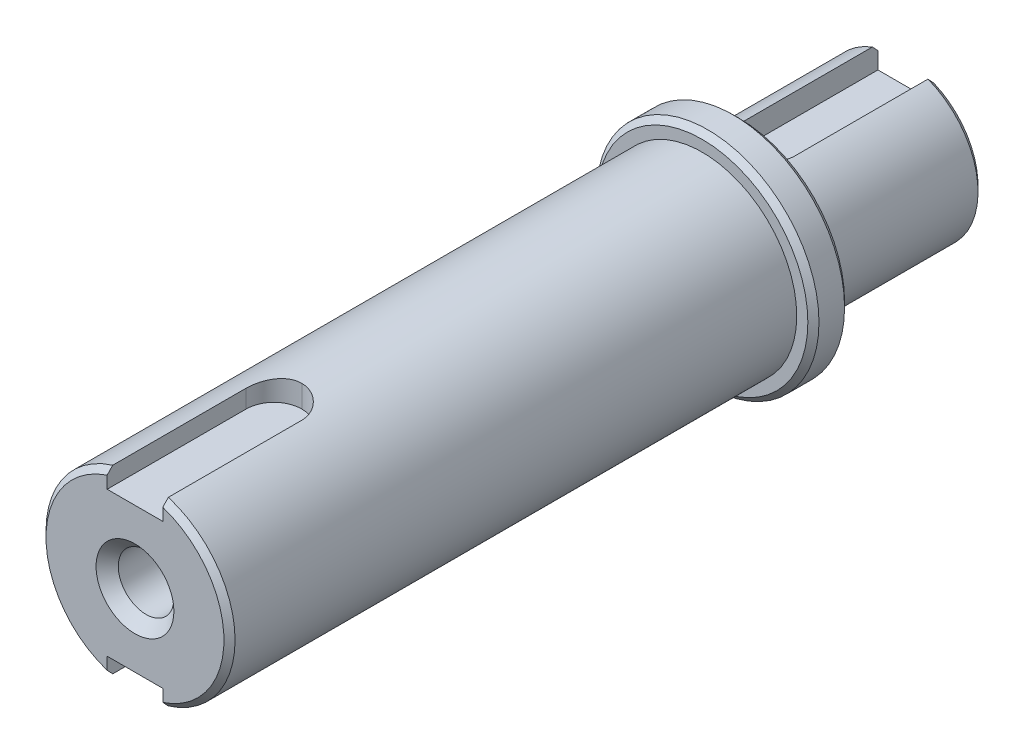
SolidWorks part; units mm, degrees
ref_plane "前视基准面" through (0, 0, 0) normal (0, 0, 1) x (1, 0, 0)
ref_plane "上视基准面" through (0, 0, 0) normal (0, 1, 0) x (1, 0, 0)
ref_plane "右视基准面" through (0, 0, 0) normal (1, 0, 0) x (0, 0, -1)
sketch "草图1" plane through (0, 0, 0) normal (0, 0, 1) x (1, 0, 0)
  circle A0 centre (0, 0) radius 7
  dimension "D1" = 14
extrude "拉伸1" add sketch "草图1" along normal blind 15
sketch "草图3" plane through (0, 0, 15) normal (0, 0, 1) x (1, 0, 0)
  circle A0 centre (0, 0) radius 10
extrude "拉伸2" add sketch "草图3" along normal blind 3.3
sketch "草图4" plane through (0, 0, 18.3) normal (0, 0, 1) x (1, 0, 0)
  circle A0 centre (0, 0) radius 8.5
extrude "拉伸3" add sketch "草图4" along normal blind 51
sketch "草图6" plane through (0, 0, 69.3) normal (0, 0, 1) x (1, 0, 0)
  line L1 (-2.5, 9.126) -> (2.5, 9.126)
  line L2 (-2.5, 9.126) -> (-2.5, 6.5)
  line L3 (-2.5, 6.5) -> (2.5, 6.5)
  line L4 (2.5, 9.126) -> (2.5, 6.5)
extrude "切除-拉伸1" cut sketch "草图6" against normal blind 15
fillet "圆角1" radius 2.5 2 edges at (-2.5, 7.312, 54.3) (2.5, 7.312, 54.3)
sketch "草图7" plane through (0, 0, 69.3) normal (0, 0, 1) x (1, 0, 0)
  circle A0 centre (0, 0) radius 2.5
  dimension "D1" = 5
extrude "切除-拉伸2" cut sketch "草图7" against normal blind 15
sketch "草图8" plane through (0, 0, 0) normal (0, 0, -1) x (-1, 0, 0)
  line L1 (-2.5, 7) -> (2.5, 7)
  line L2 (-2.5, 7) -> (-2.5, 4.5)
  line L3 (-2.5, 4.5) -> (2.5, 4.5)
  line L4 (2.5, 7) -> (2.5, 4.5)
  dimension "D2" = 2.5
extrude "切除-拉伸3" cut sketch "草图8" against normal blind 15
fillet "圆角2" radius 2.5 2 edges at (-2.5, 5.5192, 15) (2.5, 5.5192, 15)
chamfer "倒角1" distance 1 angle 45 1 edges at (2.5, 0, 69.3)
chamfer "倒角2" distance 0.5 angle 45 3 edges at (10, 0, 15) (10, 0, 18.3) (0, -8.5, 69.3)
chamfer "倒角3" distance 0.5 angle 45 1 edges at (0, -7, 0)
ref_axis "基准轴1" through (0, 0, 68.8) along (0, 0, -1)
pattern_circular "阵列(圆周)1" count 2 over 360 about axis through (0, 0, 68.8) along (0, 0, -1) of "切除-拉伸1"
fillet "圆角3" radius 2.5 2 edges at (-2.5, -7.312, 54.3) (2.5, -7.312, 54.3)
